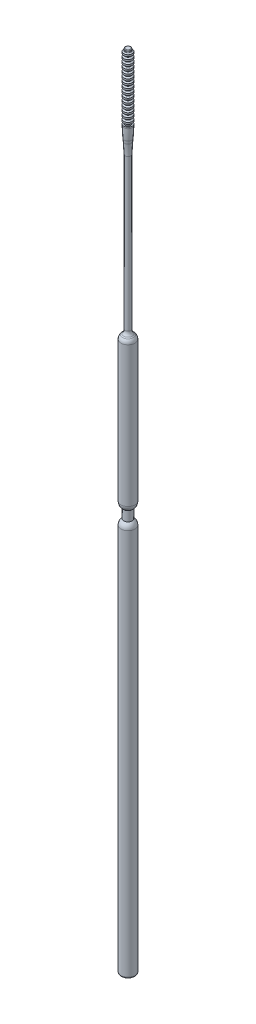
SolidWorks part; units mm, degrees
ref_plane "Front Plane" through (0, 0, 0) normal (0, 0, 1) x (1, 0, 0)
ref_plane "Top Plane" through (0, 0, 0) normal (0, 1, 0) x (1, 0, 0)
ref_plane "Right Plane" through (0, 0, 0) normal (1, 0, 0) x (0, 0, -1)
sketch "Sketch2" plane through (0, 0, 0) normal (0, 1, 0) x (1, 0, 0)
  circle A0 centre (0, 0) radius 0.5
  dimension "D1" = 1
extrude "Boss-Extrude1" add sketch "Sketch2" along normal blind 5
sketch "Sketch4" plane through (0, 0, 0) normal (1, 0, 0) x (0, 0, -1)
  line L0 (0, 5) -> (0, 10.5)
  line L1 (0.5, 5) -> (-0.5, 5) construction
  line L2 (0, 10.5) -> (0.75, 10.5)
  line L3 (0.75, 10.5) -> (0.75, 9)
  line L4 (0.5, 5) -> (0.5, 6.5)
  line L5 (0.5, 6.5) -> (0.75, 9)
  line L6 (0, 5) -> (0.5, 5)
  point P5 (0.75, 9)
  point P7 (0.5, 6.5)
  dimension "D1" = 5.5
  dimension "D2" = 0.75
  dimension "D3" = 1.5
  dimension "D4" = 1.5
  dimension "D5" = 0.5
revolve "Revolve1" add sketch "Sketch4" angle 360 about L0
fillet "Fillet1" radius 20 2 edges at (0, 9, -0.75) (0, 6.5, -0.5)
sketch "Sketch5" plane through (0, 10.5, 0) normal (0, 1, 0) x (1, 0, 0)
  line L2 (-0.125, 0.7395) -> (-0.125, -0.7395)
  line L4 (0.125, 0.7395) -> (0.125, -0.7395)
  line L5 (-0.7395, 0.125) -> (0.7395, 0.125)
  line L7 (-0.7395, -0.125) -> (0.7395, -0.125)
  circle A0 centre (0, 0) radius 0.75
  circle A1 centre (0, 0) radius 0.5
  circle A2 centre (0, 0) radius 0.5
  dimension "D1" = 1
  dimension "D6" = 1.5
  dimension "0.5" = 1
  dimension "D2" = 0.125
  dimension "D3" = 0.25
  dimension "D4" = 0.125
  dimension "D5" = 0.25
extrude "Boss-Extrude3" add sketch "Sketch5" along normal blind 1 contours L4 A2 L2 L5 | L7 A2 L5 L4 | L5 A2 L4 | L4 A2 L7 | L2 A2 L4 L7 | L2 L7 L4 L5 | L5 A2 L7 L2 | L2 A2 L5 | L7 A2 L2
sketch "Sketch10" plane through (0, 0, 0) normal (0, 0, 1) x (1, 0, 0)
  line L0 (0, 11.5) -> (0.75, 10.9748)
  line L1 (0.5, 11.5) -> (-0.5, 11.5) construction
  line L2 (0.75, 10.6697) -> (0.75, 10.9748)
  line L3 (0, 11.1948) -> (0.75, 10.6697)
  line L4 (0, 11.5) -> (0, 11.1948)
  dimension "D1" = 35
  dimension "D2" = 0.25
revolve "Revolve5" add sketch "Sketch10" angle 360 about L4
other "Move Face1" face at (0, 10.5, 0.5) parameters "D1"=0.25
sketch "Sketch8" plane through (0, 0, 0) normal (0, -1, 0) x (-1, 0, 0)
  circle A0 centre (0, 0) radius 0.5
extrude "Boss-Extrude4" add sketch "Sketch8" along normal blind 21.5
sketch "Sketch9" plane through (0, 0, 0) normal (0, 0, 1) x (1, 0, 0)
  line L0 (-0.5, -21.5) -> (-0.5, -22)
  line L1 (-0.5, -22) -> (-1.25, -22.75)
  line L2 (-1.25, -22.75) -> (-1.25, -23.25)
  line L3 (-0.5, 5.5025) -> (-0.5, -21.5) construction
  line L4 (-1.25, -23.25) -> (-1.25, -48.25)
  line L5 (-0.5, -21.5) -> (0, -21.5)
  line L6 (0, -48.25) -> (0, -52)
  line L8 (-1.25, -52) -> (-1.25, -120.25)
  line L9 (-1.25, -120.25) -> (-1.25, -121.5)
  line L10 (0, -21.5) -> (0, -121.5)
  line L11 (-0.5, -21.5) -> (0.5, -21.5) construction
  line L12 (0, -121.5) -> (-1.25, -121.5)
  line L13 (-0.75, -49.25) -> (-0.75, -51)
  arc A1 (-0.75, -51) -> (-1.25, -52) centre (0, -52) ccw
  arc A2 (-1.25, -48.25) -> (-0.75, -49.25) centre (0, -48.25) ccw
  dimension "D7" = 3.75
  dimension "D10" = 0.75
  dimension "D1" = 0.75
  dimension "D2" = 0.5
  dimension "D3" = 0.5
  dimension "D4" = 0.75
  dimension "D5" = 25
  dimension "D6" = 1.25
  dimension "D8" = 68.25
  dimension "D9" = 1.25
  dimension "D11" = 0.75
revolve "Revolve4" add sketch "Sketch9" angle 360 about L10
fillet "Fillet6" radius 0.25 1 edges at (0, -121.5, 1.25)
fillet "Fillet7" radius 1 2 edges at (0, -22.75, 1.25) (0, -22, 0.5)
pattern_linear "LPattern1" count 15 spacing 0.75 along (0, 1, 0) of "Revolve5", "Boss-Extrude3"
fillet "Fillet8" radius 0.1 2 edges at (0.5, 21.6499, 0) (0, 22, 0.5)
